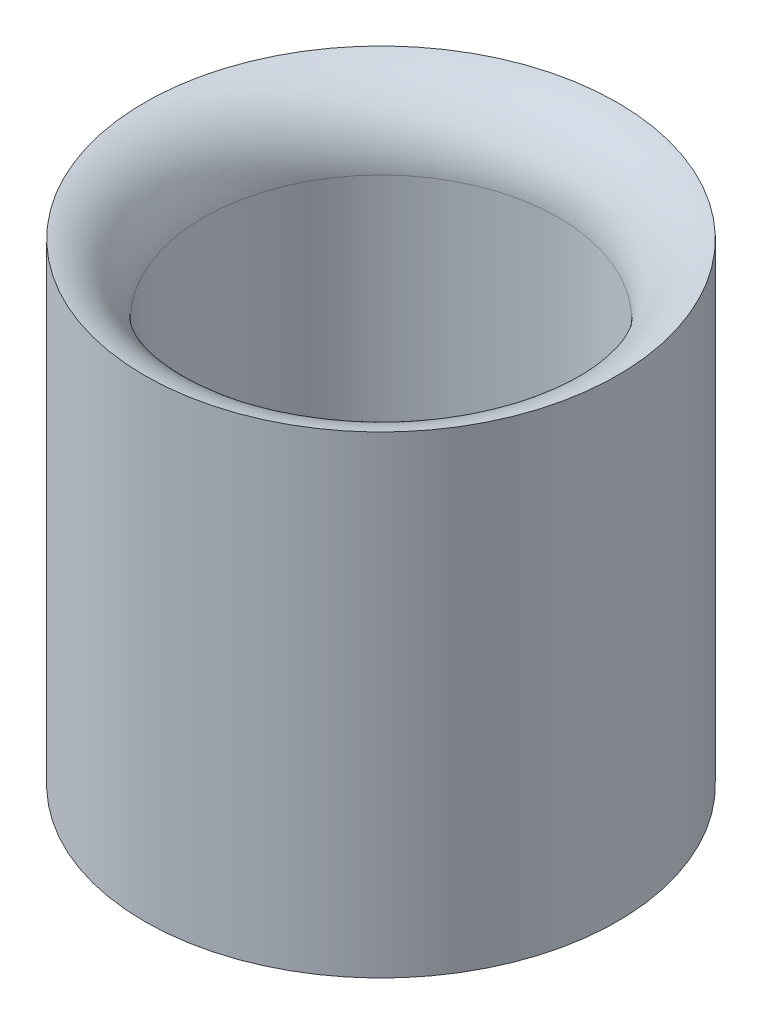
SolidWorks part; units mm, degrees
ref_plane "Front Plane" through (0, 0, 0) normal (0, 0, 1) x (1, 0, 0)
ref_plane "Top Plane" through (0, 0, 0) normal (0, 1, 0) x (1, 0, 0)
ref_plane "Right Plane" through (0, 0, 0) normal (1, 0, 0) x (0, 0, -1)
sketch "Sketch1" plane through (0, 0, 0) normal (0, 1, 0) x (1, 0, 0)
  circle A0 centre (0, 0) radius 10
  dimension "D1" = 20
extrude "Boss-Extrude1" add sketch "Sketch1" along normal blind 20 contours A0
sketch "Sketch2" plane through (0, 20, 0) normal (0, 1, 0) x (1, 0, 0)
  circle A0 centre (0, 0) radius 7.5
  dimension "D1" = 15
extrude "Cut-Extrude1" cut sketch "Sketch2" against normal up to next
fillet "Fillet1" radius 3 1 edges at (0, 20, 7.5)
